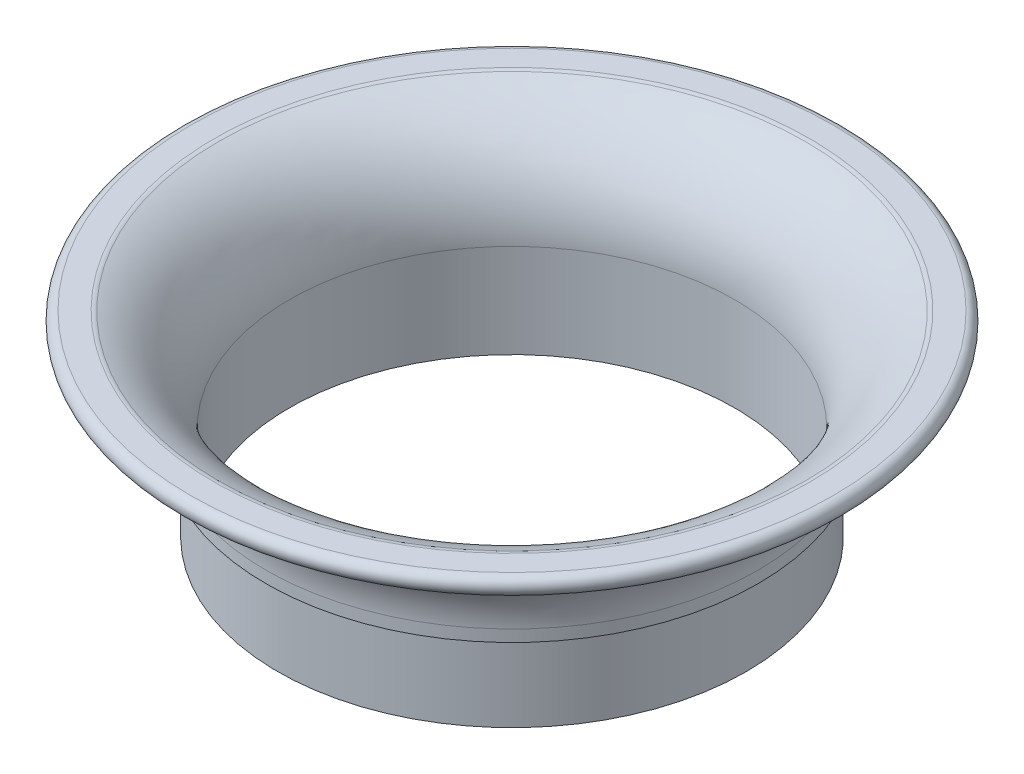
SolidWorks part; units mm, degrees
ref_plane "Front Plane" through (0, 0, 0) normal (0, 0, 1) x (1, 0, 0)
ref_plane "Top Plane" through (0, 0, 0) normal (0, 1, 0) x (1, 0, 0)
ref_plane "Right Plane" through (0, 0, 0) normal (1, 0, 0) x (0, 0, -1)
sketch "Sketch1" plane through (0, 0, 0) normal (0, 0, 1) x (1, 0, 0)
  line L13 (0, -12.7) -> (0, 12.7) construction
  line L14 (0, -12.7) -> (-60.325, -12.7) construction
  line L16 (-60.325, -12.7) -> (-60.325, 12.7)
  line L17 (-60.325, -12.7) -> (-63.5, -12.7)
  line L18 (-63.5, -12.7) -> (-63.5, 9.525)
  line L22 (-63.5, 9.525) -> (-66.675, 9.525)
  line L23 (-66.675, 12.7) -> (-66.675, 9.525)
  line L25 (0, 12.7) -> (0, 40.3323)
  line L26 (-80.6502, 40.3323) -> (-87.0002, 40.3323)
  line L28 (0, 40.3323) -> (-79.7854, 40.3323) construction
  arc A2 (-60.325, 12.7) -> (-79.5684, 40.1423) centre (-89.514, 12.7) ccw
  arc A3 (-66.675, 12.7) -> (-86.8658, 35.3849) centre (-89.514, 12.7) ccw
  arc A4 (-87.0002, 40.3323) -> (-86.8658, 35.3849) centre (-86.8113, 37.8619) ccw
  arc A8 (-60.325, 12.7) -> (-86.1295, 41.6921) centre (-89.514, 12.7) ccw construction
  arc A9 (-79.5684, 40.1423) -> (-80.6502, 40.3323) centre (-80.6502, 37.1573) ccw
  point P3 (0, 0)
  point P16 (0, 0)
  point P22 (-66.675, 12.7)
  point P23 (-90.3267, 40.22)
  point P24 (-60.325, 12.7)
  point P25 (-80.8205, 40.3934)
  point P26 (-87.6708, 35.4676)
  point P27 (-85.3754, 37.6319)
  point P28 (-85.9843, 37.7004)
  point P29 (-85.9843, 37.7004)
  point P30 (-86.8658, 40.2235)
  point P32 (-85.1566, 39.6514)
  point P33 (-86.8658, 37.8619)
  dimension "D5" = 22.225
  dimension "D8" = 3.175
  dimension "D9" = 22.839
  dimension "D10" = 2.4776
  dimension "D1" = 25.4
  dimension "D2" = 127
  dimension "D3" = 3.175
  dimension "D4" = 25.4
  dimension "D6" = 6.35
  dimension "D7" = 6.35
  dimension "D11" = 25.8599
revolve "Revolve1" add sketch "Sketch1" angle 360 about L13
